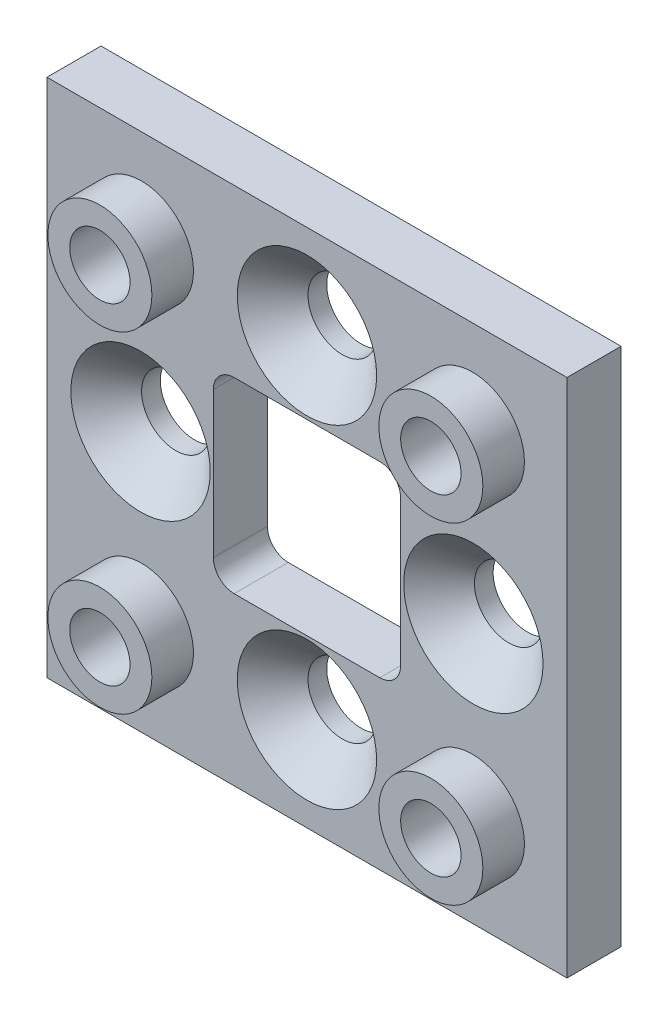
SolidWorks part; units mm, degrees
ref_plane "前视基准面" through (0, 0, 0) normal (0, 0, 1) x (1, 0, 0)
ref_plane "上视基准面" through (0, 0, 0) normal (0, 1, 0) x (1, 0, 0)
ref_plane "右视基准面" through (0, 0, 0) normal (1, 0, 0) x (0, 0, -1)
sketch "草图1" plane through (0, 0, 0) normal (0, 0, 1) x (1, 0, 0)
  line L1 (-12.5, 12.5) -> (12.5, 12.5)
  line L2 (-12.5, 12.5) -> (-12.5, -12.5)
  line L3 (-12.5, -12.5) -> (12.5, -12.5)
  line L4 (12.5, 12.5) -> (12.5, -12.5)
  line L5 (-12.5, 12.5) -> (12.5, -12.5) construction
  line L6 (-12.5, -12.5) -> (12.5, 12.5) construction
  line L7 (-4.5, 4.5) -> (4.5, 4.5)
  line L8 (-4.5, 4.5) -> (-4.5, -4.5)
  line L9 (-4.5, -4.5) -> (4.5, -4.5)
  line L10 (4.5, 4.5) -> (4.5, -4.5)
  line L11 (-4.5, 4.5) -> (4.5, -4.5) construction
  line L12 (-4.5, -4.5) -> (4.5, 4.5) construction
  circle A0 centre (0, 8) radius 1.65
  circle A1 centre (8, 0) radius 1.65
  circle A2 centre (0, -8) radius 1.65
  circle A3 centre (-8, 0) radius 1.65
  circle A4 centre (7.955, 7.955) radius 1.45
  circle A5 centre (7.955, -7.955) radius 1.45
  circle A6 centre (-7.955, -7.955) radius 1.45
  circle A7 centre (-7.955, 7.955) radius 1.45
  point P0 (0, 0)
  point P6 (0, 0)
  point P22 (0, 0)
  point P31 (0, 0)
  dimension "D9" = 2.9
  dimension "D10" = 3.3
  dimension "D1" = 25
  dimension "D2" = 25
  dimension "D3" = 9
  dimension "D4" = 9
  dimension "D6" = 16
  dimension "D8" = 22.5
  dimension "D5" = 4
  dimension "D7" = 4
extrude "凸台-拉伸1" add sketch "草图1" along normal blind 2.6
chamfer "倒角1" distance 1.7 angle 45 4 edges at (1.65, 8, 2.6) (1.65, -8, 2.6) (9.65, 0, 2.6) (-6.35, 0, 2.6)
fillet "圆角1" radius 1 4 edges at (-4.5, -4.5, 1.3) (4.5, 4.5, 1.3) (4.5, -4.5, 1.3) (-4.5, 4.5, 1.3)
sketch "草图2" plane through (0, 0, 2.6) normal (0, 0, 1) x (1, 0, 0)
  circle A0 centre (-7.955, 7.955) radius 2.5
  circle A1 centre (7.955, 7.955) radius 2.5
  circle A2 centre (7.955, -7.955) radius 2.5
  circle A3 centre (7.955, -7.955) radius 1.45 construction
  circle A4 centre (-7.955, -7.955) radius 2.5
  circle M2 centre (-7.955, -7.955) radius 1.45
  circle M3 centre (7.955, 7.955) radius 1.45
  circle M24 centre (7.955, -7.955) radius 1.45
  circle M25 centre (-7.955, 7.955) radius 1.45
  dimension "D1" = 5
extrude "凸台-拉伸2" add sketch "草图2" along normal blind 2 contours A4 M2 | A0 M25 | A1 M3 | A2 M24 region at (-10.3842, 7.955, 2.6) region at (5.5257, 7.955, 2.6) region at (5.5257, -7.955, 2.6) region at (-10.3842, -7.955, 2.6)
